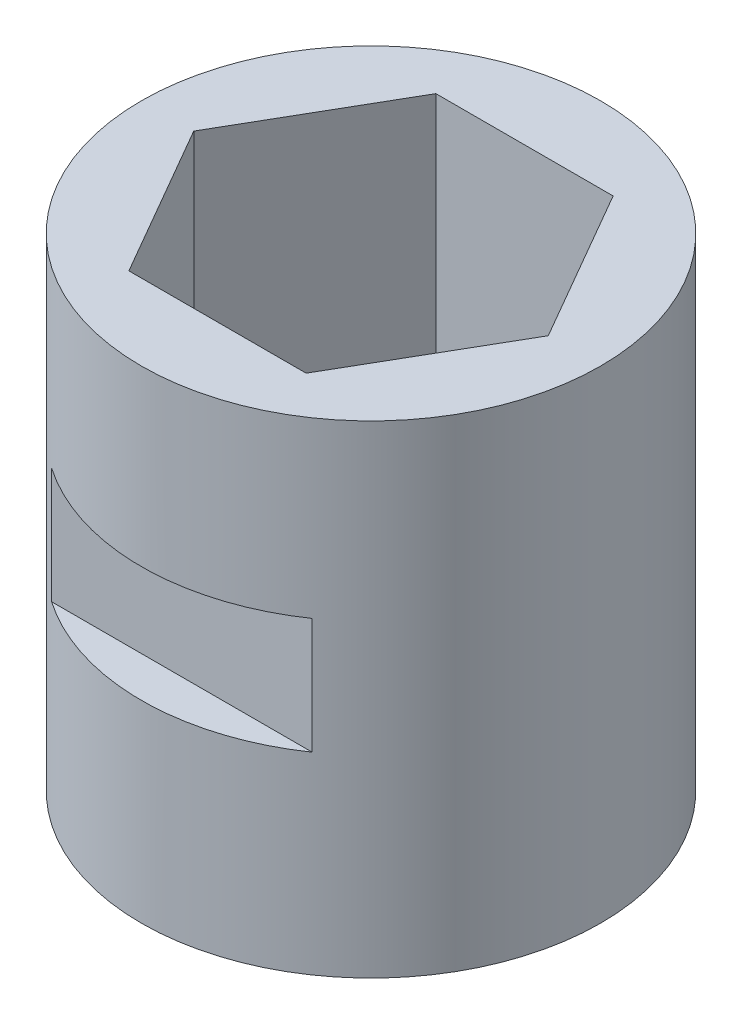
SolidWorks part; units mm, degrees
material "Polyester Resin"
ref_plane "Front Plane" through (0, 0, 0) normal (0, 0, 1) x (1, 0, 0)
ref_plane "Top Plane" through (0, 0, 0) normal (0, 1, 0) x (1, 0, 0)
ref_plane "Right Plane" through (0, 0, 0) normal (1, 0, 0) x (0, 0, -1)
sketch "Sketch1" plane through (0, 0, 0) normal (0, 1, 0) x (1, 0, 0)
  line L1 (-2.9156, 5.05) -> (-5.8312, 0)
  line L2 (-5.8312, 0) -> (-2.9156, -5.05)
  line L3 (-2.9156, -5.05) -> (2.9156, -5.05)
  line L4 (2.9156, -5.05) -> (5.8312, 0)
  line L5 (5.8312, 0) -> (2.9156, 5.05)
  line L6 (2.9156, 5.05) -> (-2.9156, 5.05)
  circle A0 centre (0, 0) radius 5.05 construction
  circle A1 centre (0, 0) radius 7.5565
  dimension "D2" = 15.113
  dimension "D1" = 10.1
extrude "Boss-Extrude1" add sketch "Sketch1" along normal blind 12.7
sketch "Sketch2" plane through (0, 0, 0) normal (0, -1, 0) x (1, 0, 0)
  circle A0 centre (0, 0) radius 7.5565
  circle A1 centre (0, 0) radius 3.3
  dimension "D1" = 6.6
extrude "Boss-Extrude2" add sketch "Sketch2" along normal blind 3.175
sketch "Sketch3" plane through (0, 0, 0) normal (1, 0, 0) x (0, 0, -1)
  line L0 (-6.223, 6.985) -> (-6.223, 3.175)
  line L1 (6.223, 6.985) -> (6.223, 3.175)
  line L2 (-7.5565, -3.175) -> (7.5565, -3.175) construction
  line L3 (-6.223, 6.985) -> (-8.202, 6.985)
  line L4 (-8.202, 6.985) -> (-8.202, 3.175)
  line L5 (-8.202, 3.175) -> (-6.223, 3.175)
  line L6 (6.223, 6.985) -> (8.4791, 6.985)
  line L7 (8.4791, 6.985) -> (8.4791, 3.175)
  line L8 (8.4791, 3.175) -> (6.223, 3.175)
  dimension "D1" = 12.446
  dimension "D2" = 6.223
  dimension "D3" = 3.81
  dimension "D4" = 3.81
  dimension "D5" = 6.35
  dimension "D6" = 6.35
extrude "Cut-Extrude1" cut sketch "Sketch3" against normal through all and the other way through all
equation "\"AB_Central_Bushing_Length\" = .75in"
equation "\"Solid_Length\"= .125in"
equation "\"Hex_Length\"= .5"
equation "\"D1@Boss-Extrude1\"= \"Hex_Length\""
equation "\"D1@Boss-Extrude2\"=\"Solid_Length\""
equation "\"Cutout_Angle\" = 80"
